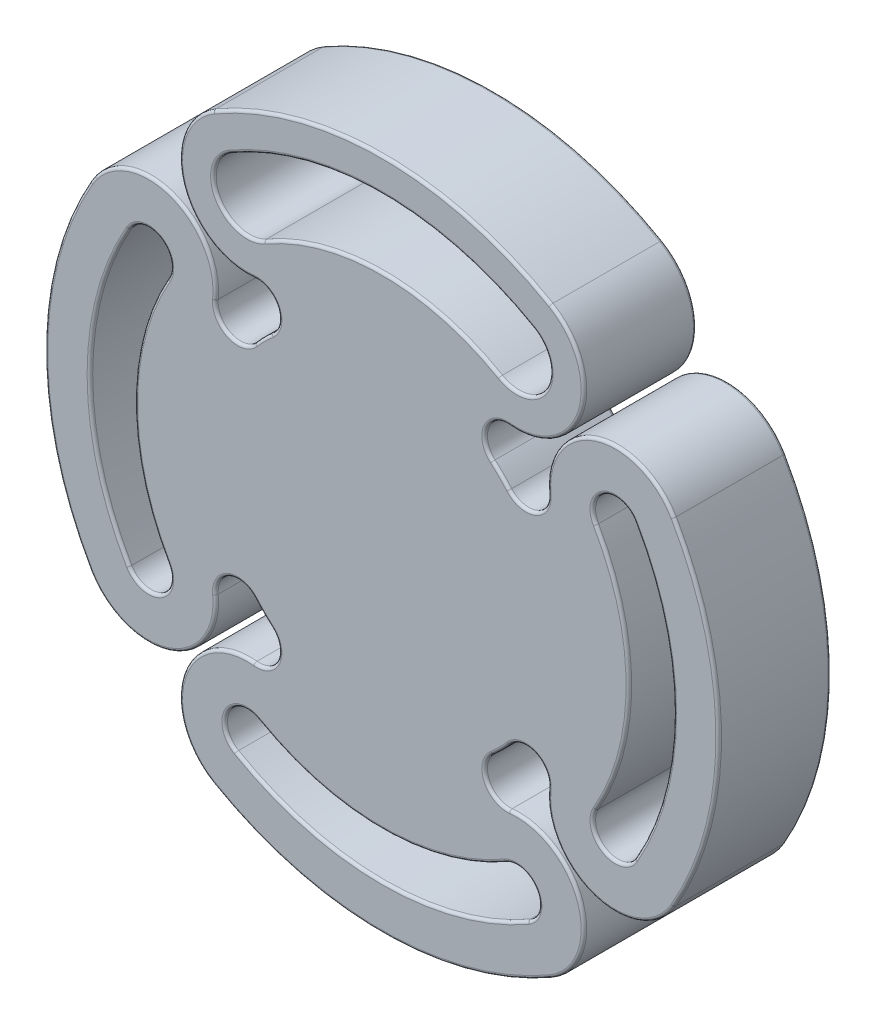
SolidWorks part; units mm, degrees
note: The reader was unsure of these and kept them because the rebuilt part matched: shared geometry of "Sketch1<3>".
ref_plane "Front Plane" through (0, 0, 0) normal (0, 0, 1) x (1, 0, 0)
ref_plane "Top Plane" through (0, 0, 0) normal (0, 1, 0) x (1, 0, 0)
ref_plane "Right Plane" through (0, 0, 0) normal (1, 0, 0) x (0, 0, -1)
sketch "Sketch1" plane through (0, 0, 0) normal (0, 0, 1) x (1, 0, 0)
  line L0 (0, 69239.6659) -> (0, -69239.6659) construction
  line L1 (0, 0) -> (-69239.4435, 0) construction
  arc A5 (-9.8415, 11.3202) -> (9.8415, 11.3202) centre (0, 0) ccw
  arc A6 (12, 20.7846) -> (-12, 20.7846) centre (0, 0) ccw construction
  arc A7 (15, 25.9808) -> (-15, 25.9808) centre (0, 0) ccw
  arc A9 (11.3652, 14.8183) -> (15, 25.9808) centre (12, 20.7846) ccw
  arc A10 (-15, 25.9808) -> (-11.3652, 14.8183) centre (-12, 20.7846) ccw
  arc A11 (12, 20.7846) -> (-12, 20.7846) centre (0, 0) ccw construction
  arc A12 (13.5, 23.3827) -> (-13.5, 23.3827) centre (0, 0) ccw
  arc A13 (10.5, 18.1865) -> (-10.5, 18.1865) centre (0, 0) ccw
  arc A14 (10.5, 18.1865) -> (13.5, 23.3827) centre (12, 20.7846) ccw
  arc A15 (-13.5, 23.3827) -> (-10.5, 18.1865) centre (-12, 20.7846) ccw
  arc A16 (-11.3652, 14.8183) -> (-9.8415, 11.3202) centre (-11.1536, 12.8295) cw
  arc A17 (11.3652, 14.8183) -> (9.8415, 11.3202) centre (11.1536, 12.8295) ccw
  arc A18 (14.8183, -11.3652) -> (25.9808, -15) centre (20.7846, -12) ccw
  arc A19 (25.9808, 15) -> (14.8183, 11.3652) centre (20.7846, 12) ccw
  arc A20 (20.7846, -12) -> (20.7846, 12) centre (0, 0) ccw construction
  arc A21 (25.9808, -15) -> (25.9808, 15) centre (0, 0) ccw
  arc A22 (14.8183, 11.3652) -> (11.3202, 9.8415) centre (12.8295, 11.1536) cw
  arc A23 (14.8183, -11.3652) -> (11.3202, -9.8415) centre (12.8295, -11.1536) ccw
  arc A24 (20.7846, -12) -> (20.7846, 12) centre (0, 0) ccw construction
  arc A25 (23.3827, -13.5) -> (23.3827, 13.5) centre (0, 0) ccw
  arc A26 (18.1865, -10.5) -> (18.1865, 10.5) centre (0, 0) ccw
  arc A27 (18.1865, -10.5) -> (23.3827, -13.5) centre (20.7846, -12) ccw
  arc A28 (23.3827, 13.5) -> (18.1865, 10.5) centre (20.7846, 12) ccw
  arc A29 (-11.3652, -14.8183) -> (-15, -25.9808) centre (-12, -20.7846) ccw
  arc A30 (15, -25.9808) -> (11.3652, -14.8183) centre (12, -20.7846) ccw
  arc A31 (-12, -20.7846) -> (12, -20.7846) centre (0, 0) ccw construction
  arc A32 (-15, -25.9808) -> (15, -25.9808) centre (0, 0) ccw
  arc A33 (11.3652, -14.8183) -> (9.8415, -11.3202) centre (11.1536, -12.8295) cw
  arc A34 (-11.3652, -14.8183) -> (-9.8415, -11.3202) centre (-11.1536, -12.8295) ccw
  arc A35 (-12, -20.7846) -> (12, -20.7846) centre (0, 0) ccw construction
  arc A36 (-13.5, -23.3827) -> (13.5, -23.3827) centre (0, 0) ccw
  arc A37 (-10.5, -18.1865) -> (10.5, -18.1865) centre (0, 0) ccw
  arc A38 (-10.5, -18.1865) -> (-13.5, -23.3827) centre (-12, -20.7846) ccw
  arc A39 (13.5, -23.3827) -> (10.5, -18.1865) centre (12, -20.7846) ccw
  arc A40 (-14.8183, 11.3652) -> (-25.9808, 15) centre (-20.7846, 12) ccw
  arc A41 (-25.9808, -15) -> (-14.8183, -11.3652) centre (-20.7846, -12) ccw
  arc A42 (-20.7846, 12) -> (-20.7846, -12) centre (0, 0) ccw construction
  arc A43 (-25.9808, 15) -> (-25.9808, -15) centre (0, 0) ccw
  arc A44 (-14.8183, -11.3652) -> (-11.3202, -9.8415) centre (-12.8295, -11.1536) cw
  arc A45 (-14.8183, 11.3652) -> (-11.3202, 9.8415) centre (-12.8295, 11.1536) ccw
  arc A46 (-20.7846, 12) -> (-20.7846, -12) centre (0, 0) ccw construction
  arc A47 (-23.3827, 13.5) -> (-23.3827, -13.5) centre (0, 0) ccw
  arc A48 (-18.1865, 10.5) -> (-18.1865, -10.5) centre (0, 0) ccw
  arc A49 (-18.1865, 10.5) -> (-23.3827, 13.5) centre (-20.7846, 12) ccw
  arc A50 (-23.3827, -13.5) -> (-18.1865, -10.5) centre (-20.7846, -12) ccw
  point P4 (0, 24)
  point P13 (0, 24)
  point P24 (0, 0)
  point P31 (24, 0)
  point P34 (24, 0)
  point P49 (0, -24)
  point P52 (0, -24)
  point P67 (-24, 0)
  point P70 (-24, 0)
  point P83 (0, 0)
  dimension "D1" = 3
  dimension "D3" = 60
  dimension "D4" = 60
  dimension "D2" = 6
  dimension "D6" = 2
  dimension "30" = 30
  dimension "D7" = 4
  dimension "D8" = 30
  dimension "D9" = 27
  dimension "D5" = 24
extrude "Extrude-Thin1" add sketch "Sketch1" along normal mid plane 10 thin contours A47 A50 A48 A49 | A25 A28 A26 A27 | A36 A39 A37 A38
extrude "Boss-Extrude1" add sketch "Sketch1<3>" along normal mid plane 10 contours A17 A9 A7 A10 A16 A5 A15 A12 A14 A13 | A45 A40 A43 A41 A44 A5 A50 A47 A49 A48 | A23 A18 A21 A19 A22 A5 A28 A25 A27 A26 | A34 A29 A32 A30 A33 A5 A39 A36 A38 A37
sketch "Sketch1<3>" plane through (0, 0, 0) normal (0, 0, 1) x (1, 0, 0) same geometry as "Sketch1"
fillet "Fillet1" radius 0.25 80 edges at (0, -22, -5) (0, -22, 5) (10.6066, -10.6066, -5) (10.6066, -10.6066, 5) (0, -30, -5) (0, -30, 5) (-10.6066, -10.6066, -5) (-10.6066, -10.6066, 5) (0, 27, -5) (0, 27, 5) (-30, 0, -5) (-30, 0, 5) (0, -26, -5) (0, -26, 5) (13.7321, -19.7846, -5) (13.7321, -19.7846, 5) (-13.7321, -19.7846, -5) (-13.7321, -19.7846, 5) (26, 0, -5) (26, 0, 5) (19.7846, 13.7321, -5) (19.7846, 13.7321, 5) (22, 0, -5) (22, 0, 5) (19.7846, -13.7321, -5) (19.7846, -13.7321, 5) (9.3201, 13.6282, -5) (9.3201, 13.6282, 5) (17.7052, 18.9269, -5) (17.7052, 18.9269, 5) (0, 30, -5) (0, 30, 5) (-17.7052, 18.9269, -5) (-17.7052, 18.9269, 5) (-9.3201, 13.6282, -5) (-9.3201, 13.6282, 5) (-10.6066, 10.6066, -5) (-10.6066, 10.6066, 5) (-13.6282, 9.3201, -5) (-13.6282, 9.3201, 5) (-18.9269, 17.7052, -5) (-18.9269, 17.7052, 5) (-18.9269, -17.7052, -5) (-18.9269, -17.7052, 5) (-13.6282, -9.3201, -5) (-13.6282, -9.3201, 5) (-9.3201, -13.6282, -5) (-9.3201, -13.6282, 5) (-17.7052, -18.9269, -5) (-17.7052, -18.9269, 5) (17.7052, -18.9269, -5) (17.7052, -18.9269, 5) (9.3201, -13.6282, -5) (9.3201, -13.6282, 5) (13.6282, -9.3201, -5) (13.6282, -9.3201, 5) (18.9269, -17.7052, -5) (18.9269, -17.7052, 5) (30, 0, -5) (30, 0, 5) (18.9269, 17.7052, -5) (18.9269, 17.7052, 5) (13.6282, 9.3201, -5) (13.6282, 9.3201, 5) (10.6066, 10.6066, -5) (10.6066, 10.6066, 5) (-14.5981, 19.2846, -5) (-14.5981, 19.2846, 5) (14.5981, 19.2846, -5) (14.5981, 19.2846, 5) (0, 21, -5) (0, 21, 5) (-26, 0, -5) (-26, 0, 5) (-19.7846, -13.7321, -5) (-19.7846, -13.7321, 5) (-22, 0, -5) (-22, 0, 5) (-19.7846, 13.7321, -5) (-19.7846, 13.7321, 5)
